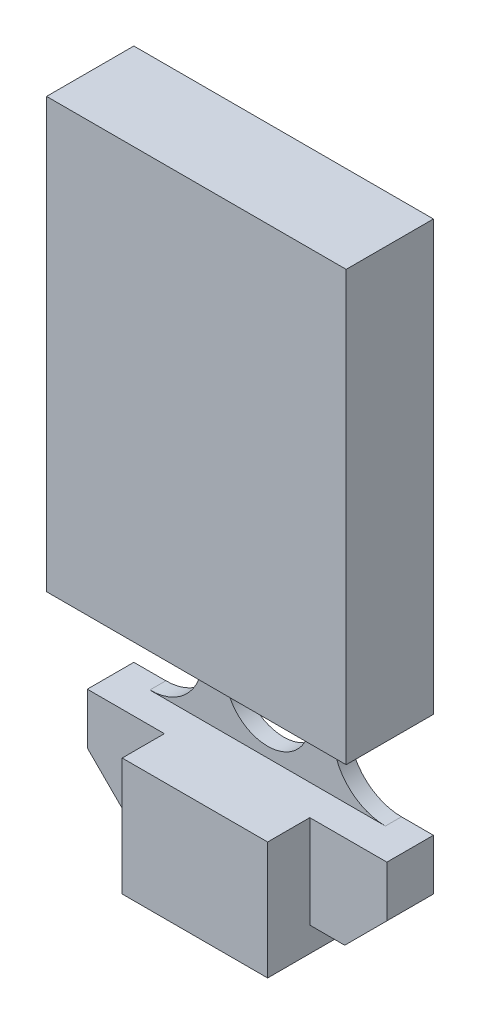
SolidWorks part; units mm, degrees
ref_plane "Front Plane" through (0, 0, 0) normal (0, 0, 1) x (1, 0, 0)
ref_plane "Top Plane" through (0, 0, 0) normal (0, 1, 0) x (1, 0, 0)
ref_plane "Right Plane" through (0, 0, 0) normal (1, 0, 0) x (0, 0, -1)
sketch "Sketch1" plane through (0, 0, 0) normal (0, 0, 1) x (1, 0, 0)
  line L1 (0, 0) -> (20.6, 0)
  line L2 (0, 0) -> (0, 43.1)
  line L3 (0, 43.1) -> (20.6, 43.1)
  line L4 (20.6, 0) -> (20.6, 43.1)
  dimension "D1" = 43.1
  dimension "D2" = 20.6
extrude "Boss-Extrude1" add sketch "Sketch1" along normal blind 1.1
sketch "Sketch2" plane through (0, 0, 1.1) normal (0, 0, 1) x (1, 0, 0)
  line L0 (20.6, 0) -> (20.6, 43.1) construction
  line L1 (0, 43.1) -> (20.6, 43.1)
  line L2 (0, 43.1) -> (0, 13.6)
  line L3 (0, 13.6) -> (20.6, 13.6)
  line L4 (20.6, 43.1) -> (20.6, 13.6)
  dimension "D1" = 29.5
extrude "Boss-Extrude2" add sketch "Sketch2" along normal blind 4.9
sketch "Sketch3" plane through (0, 0, 1.1) normal (0, 0, 1) x (1, 0, 0)
  line L0 (10.3, 43.1) -> (10.3, 0) construction
  line L1 (20.6, 43.1) -> (0, 43.1) construction
  line L2 (0, 0) -> (20.6, 0) construction
  line L3 (0, 10) -> (20.6, 10) construction
  line L4 (0, 13.6) -> (0, 0) construction
  line L5 (20.6, 0) -> (20.6, 13.6) construction
  line L6 (0, 13.6) -> (2.2, 13.6)
  line L7 (0, 13.6) -> (20.6, 13.6) construction
  line L8 (2.2, 6.4) -> (0, 6.4)
  line L9 (0, 6.4) -> (0, 13.6)
  line L10 (20.6, 13.6) -> (18.4, 13.6)
  line L11 (18.4, 6.4) -> (20.6, 6.4)
  line L12 (20.6, 6.4) -> (20.6, 13.6)
  circle A0 centre (10.3, 10) radius 2.9
  arc A1 (2.2, 13.6) -> (2.2, 6.4) centre (2.2, 10) cw
  arc A2 (18.4, 13.6) -> (18.4, 6.4) centre (18.4, 10) ccw
  dimension "D1" = 5.8
  dimension "D3" = 16.2
  dimension "D2" = 7.2
extrude "Cut-Extrude1" cut sketch "Sketch3" against normal blind 4.9
sketch "Sketch4" plane through (0, 0, 1.1) normal (0, 0, 1) x (1, 0, 0)
  line L0 (10.3, 0) -> (10.3, 43.1) construction
  line L1 (5.3, -1.7) -> (15.3, -1.7)
  line L2 (5.3, -1.7) -> (5.3, 6.4)
  line L3 (5.3, 6.4) -> (15.3, 6.4)
  line L4 (15.3, -1.7) -> (15.3, 6.4)
  line L5 (0, 0) -> (20.6, 0) construction
  line L6 (20.6, 43.1) -> (0, 43.1) construction
  line L7 (0, 6.4) -> (20.6, 6.4) construction
  dimension "D1" = 8.1
  dimension "D2" = 10
  dimension "D3" = 5
extrude "Boss-Extrude3" add sketch "Sketch4" along normal blind 5
sketch "Sketch5" plane through (0, 0, 1.1) normal (0, 0, 1) x (1, 0, 0)
  line L1 (0, 6.4) -> (20.6, 6.4)
  line L2 (0, 6.4) -> (0, 0)
  line L3 (0, 0) -> (20.6, 0)
  line L4 (20.6, 6.4) -> (20.6, 0)
extrude "Boss-Extrude4" add sketch "Sketch5" along normal blind 2.1
sketch "Sketch6" plane through (0, 0, 3.2) normal (0, 0, 1) x (1, 0, 0)
  line L0 (0, 0) -> (0, 2.9)
  line L1 (0, 6.4) -> (0, 0) construction
  line L2 (0, 2.9) -> (2.9, 0)
  line L3 (0, 0) -> (5.3, 0) construction
  line L4 (2.9, 0) -> (0, 0)
  line L5 (20.6, 0) -> (20.6, 2.9)
  line L6 (20.6, 0) -> (20.6, 6.4) construction
  line L7 (20.6, 2.9) -> (17.7, 0)
  line L8 (15.3, 0) -> (20.6, 0) construction
  line L9 (17.7, 0) -> (20.6, 0)
  line L10 (5.3, 6.4) -> (0, 6.4) construction
  line L11 (0, 2.9) -> (20.6, 2.9) construction
  dimension "D1" = 45
  dimension "D2" = 3.5
extrude "Cut-Extrude2" cut sketch "Sketch6" against normal through all
